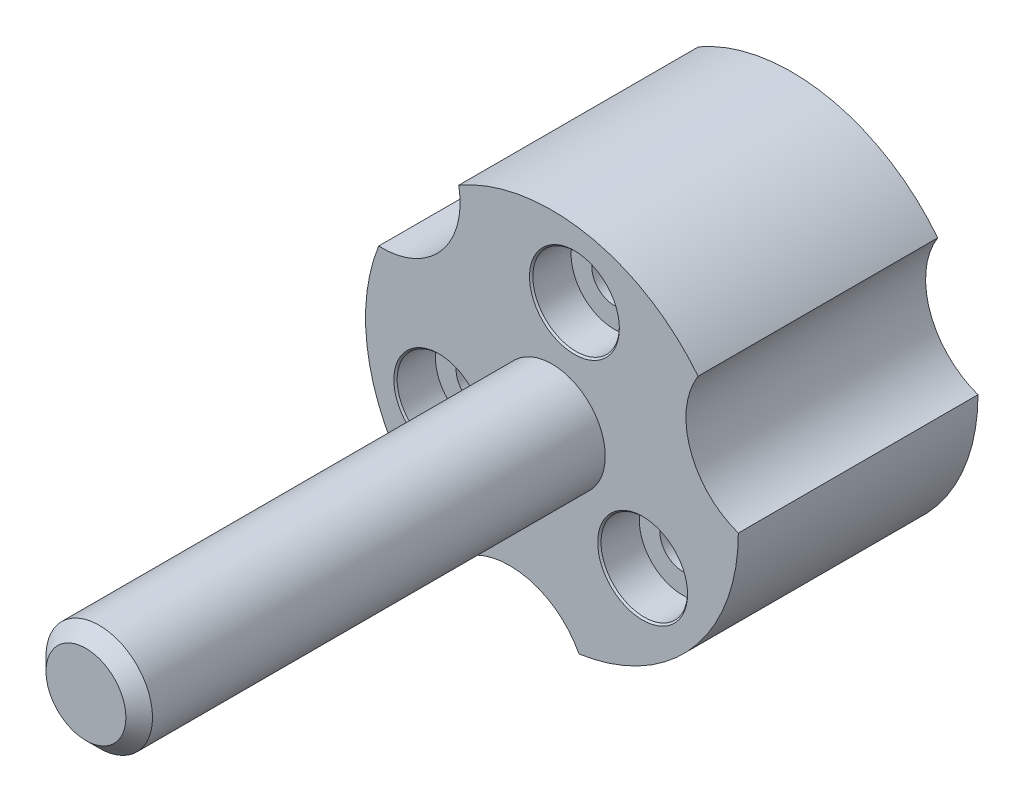
SolidWorks part; units mm, degrees
ref_plane "Plano frontal" through (0, 0, 0) normal (0, 0, 1) x (1, 0, 0)
ref_plane "Plano superior" through (0, 0, 0) normal (0, 1, 0) x (1, 0, 0)
ref_plane "Plano direito" through (0, 0, 0) normal (1, 0, 0) x (0, 0, -1)
sketch "Esboço1" plane through (0, 0, 0) normal (0, 0, 1) x (1, 0, 0)
  line L2 (10.3893, 3.6143) -> (13.2227, 4.6)
  arc A0 (10.9771, 8.6892) -> (-7, 12.1244) centre (0, 0) ccw
  arc A1 (14, 0) -> (10.9771, 8.6892) centre (15.9346, 5.5434) cw
  arc A2 (-7, -12.1244) -> (2.0365, -13.8511) centre (-3.1665, -16.5715) cw
  arc A3 (-7, 12.1244) -> (-13.0136, 5.1619) centre (-12.7681, 11.0281) cw
  arc A4 (-13.0136, 5.1619) -> (-7, -12.1244) centre (0, 0) ccw
  arc A5 (2.0365, -13.8511) -> (14, 0) centre (0, 0) ccw
  point P15 (0, 0)
  dimension "D1" = 28
  dimension "D3" = 3
  dimension "D2" = 9.2
  dimension "D4" = 3
extrude "Ressalto-extrusão1" add sketch "Esboço1" along normal blind 18 contours A2 A5 A1 A0 A3 A4 region at (0, 0, 0)
sketch "Esboço2" plane through (0, 0, 18) normal (0, 0, 1) x (1, 0, 0)
  circle A0 centre (0, 0) radius 4
  dimension "D1" = 8
extrude "Ressalto-extrusão2" add sketch "Esboço2" along normal blind 35
cosmetic thread "Representação de rosca2" parameters "D1"=25, "D2"=6.619
chamfer "Chanfro1" distance 1 angle 45 1 edges at (4, 0, 53)
sketch "Esboço3" plane through (0, 0, 18) normal (0, 0, 1) x (1, 0, 0)
  line L0 (2.0365, -13.8511) -> (14, 0)
  line L1 (0, 0) -> (8.0183, -6.9255)
  circle A0 centre (0, 0) radius 9
  arc A1 (-13.0136, 5.1619) -> (-7, -12.1244) centre (0, 0) ccw construction
  point P10 (6.8111, -5.8829)
  dimension "D1" = 5
hole_wizard "Rebaixo para SHCS M31" positions "3DSketch2" profile "Esboço5" counterbore size "M3" standard "Ansi Metric" end condition through all
sketch3d "3DSketch2"
  point P0 (6.8111, -5.8829, 18)
sketch "Esboço5" plane through (6.8111, -5.8829, 18) normal (1, 0, 0) x (0, -1, 0)
  line L0 (0, 0) -> (0, 18)
  line L1 (0, 18) -> (1.7, 18)
  line L3 (1.7, 18) -> (1.7, 3)
  line L4 (3.25, 3) -> (1.7, 3)
  line L5 (3.25, 3) -> (3.25, 0.125)
  line L6 (3.25, 0.125) -> (3.375, 0)
  line L7 (3.375, 0) -> (0, 0)
  line L8 (-3.25, 0.125) -> (-3.375, 0) construction
  line L11 (0, -6.35) -> (0, 107.95) construction
  dimension "Thru Hole Dia." = 3.4
  dimension "Thru Hole Depth" = 18
  dimension "C'Bore Dia." = 6.5
  dimension "C'Bore Depth" = 3
  dimension "Near C'Sink Dia." = 6.75
  dimension "Near C'Sink Angle" = 90
pattern_circular "PadrãoCircular1" count 3 over 360 about axis through (0, 0, 18) along (0, 0, 1) of "Rebaixo para SHCS M31"
sketch "Esboço6" plane through (0, 0, 0) normal (0, 0, -1) x (-1, 0, 0)
  circle A0 centre (0, 0) radius 6
  circle A1 centre (0, 0) radius 4
  dimension "D1" = 12
  dimension "D2" = 8
extrude "Corte-extrusão1" cut sketch "Esboço6" against normal blind 3 contours A0
extrude "Corte-extrusão2" cut sketch "Esboço6<4>" along direction (0, 0, -1) on the side against the normal blind 14 contours A1 region at (0, 0, 0)
sketch "Esboço6<4>" plane through (0, 0, 0) normal (0, 0, -1) x (-1, 0, 0) same geometry as "Esboço6"
